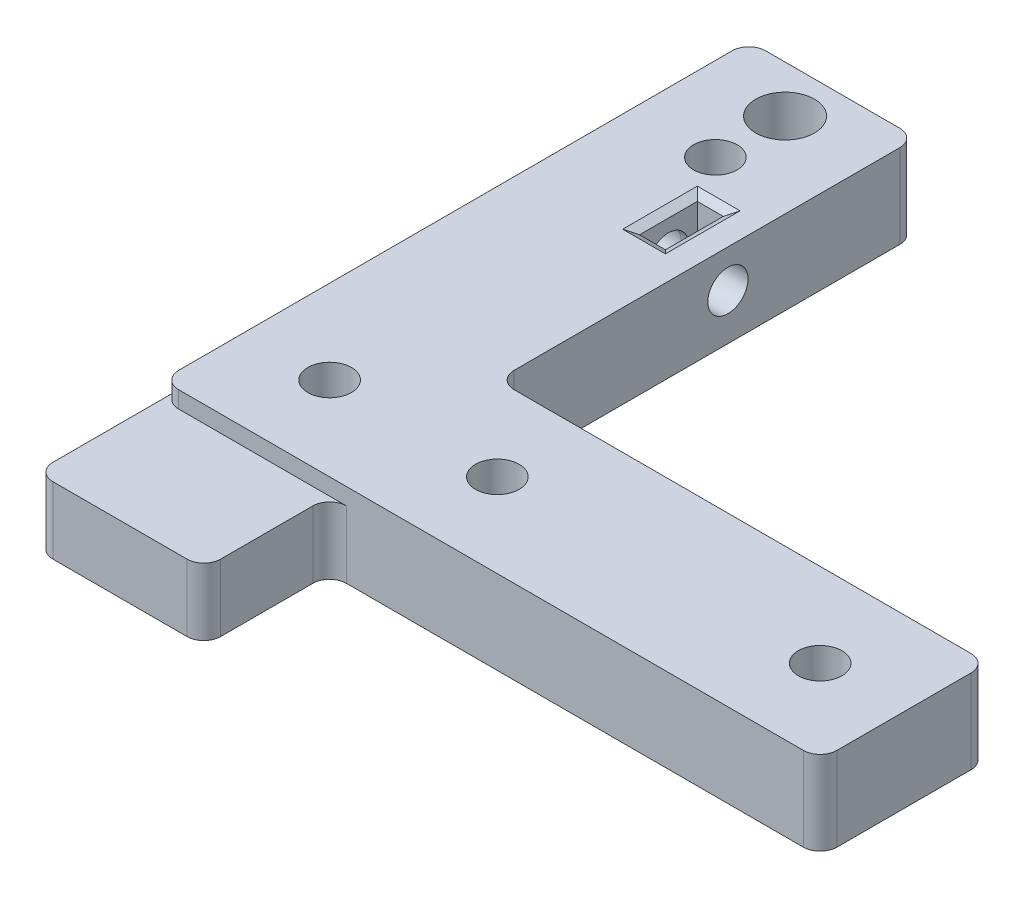
SolidWorks part; units mm, degrees
ref_plane "Front" through (0, 0, 0) normal (0, 0, 1) x (1, 0, 0)
ref_plane "Top" through (0, 0, 0) normal (0, 1, 0) x (1, 0, 0)
ref_plane "Right" through (0, 0, 0) normal (1, 0, 0) x (0, 0, -1)
sketch "Sketch1" plane through (0, 0, 0) normal (0, 1, 0) x (1, 0, 0)
  line L0 (0, 0) -> (78.5, 0)
  line L1 (78.5, 0) -> (78.5, 20)
  line L2 (78.5, 20) -> (20, 20)
  line L3 (20, 20) -> (20, 70)
  line L4 (20, 70) -> (0, 70)
  line L5 (0, 70) -> (0, 0)
  line L6 (78.5, 10) -> (0, 10) construction
  line L7 (10, 70) -> (10, 0) construction
  circle A0 centre (10, 56) radius 2.6
  circle A1 centre (68.5, 10) radius 2.6
  circle A2 centre (10, 10) radius 2.6
  circle A3 centre (30, 10) radius 2.6
  dimension "D5" = 5.2
  dimension "D6" = 10
  dimension "D7" = 20
  dimension "D1" = 78.5
  dimension "D2" = 70
  dimension "D3" = 14
  dimension "D4" = 20
extrude "Boss-Extrude1" add sketch "Sketch1" along normal blind 10
sketch "Sketch4" plane through (0, 0, 0) normal (-1, 0, 0) x (0, 0, 1)
  line L0 (-70, 10) -> (-70, 0) construction
  line L1 (-70, 10) -> (0, 10) construction
  circle A0 centre (-47.5, 5.5) radius 2.4
  dimension "D1" = 22.5
  dimension "D2" = 4.5
  dimension "D3" = 4.8
extrude "motor tensioning hole" cut sketch "Sketch4" against normal through all
sketch "Sketch10" plane through (0, 10, 0) normal (0, 1, 0) x (1, 0, 0)
  line L0 (20, 20) -> (20, 70) construction
  line L1 (0, 0) -> (20, 0)
  line L2 (0, 0) -> (0, -15)
  line L3 (0, -15) -> (20, -15)
  line L4 (20, 0) -> (20, -15)
  dimension "D1" = 15
extrude "Boss-Extrude3" add sketch "Sketch10" against normal blind 10
fillet "Fillet1" radius 2 8 edges at (0, 5, -70) (20, 5, -70) (20, 5, -20) (78.5, 5, 0) (78.5, 5, -20) (20, 5, 15) (20, 5, 0) (0, 5, 15)
chamfer "Chamfer2" distance 12 angle 5 1 edges at (0, 5.5, -45.1) first distance on face at (0, 5.5, -45.1)
sketch "Sketch17" plane through (20, 0, 0) normal (1, 0, 0) x (0, 0, -1)
  line L0 (44.05, 7.4919) -> (44.05, 10)
  line L1 (44.05, 3.5081) -> (47.5, 1.5163)
  line L2 (47.5, 1.5163) -> (50.95, 3.5081)
  line L3 (50.95, 3.5081) -> (50.95, 7.4919)
  line L4 (50.95, 7.4919) -> (47.5, 9.4837) construction
  line L5 (47.5, 9.4837) -> (44.05, 7.4919) construction
  line L6 (44.05, 7.4919) -> (44.05, 3.5081)
  line L7 (22, 10) -> (68, 10) construction
  line L8 (44.05, 10) -> (50.95, 10)
  line L9 (50.95, 10) -> (50.95, 7.4919)
  circle A0 centre (47.5, 5.5) radius 3.45 construction
  dimension "D1" = 6.9
extrude "Cut-Extrude8" cut sketch "Sketch17" against normal blind 3.1 from offset 4 offset against normal yes
chamfer "Chamfer3" distance 1 angle 30 4 edges at (14.45, 10, -44.05) (16, 10, -47.5) (14.45, 10, -50.95) (12.9, 10, -47.5) first distance on face at (10, 10, -7.4)
sketch "Sketch6" plane through (0, 10, 0) normal (0, 1, 0) x (1, 0, 0)
  line L0 (18, 70) -> (2, 70) construction
  line L1 (0, 68) -> (0, -13) construction
  circle A0 centre (9.8995, 64.4167) radius 3.5
  dimension "D1" = 5.5833
  dimension "D2" = 7
  dimension "D3" = 9.8995
extrude "M3 Screwhead Clearance" cut sketch "Sketch6" against normal blind 5
sketch "Sketch15" [suppressed] plane through (0, 10, 0) normal (0, 1, 0) x (1, 0, 0)
  line L0 (10, 56) -> (10, 63) construction
  line L1 (7.4, 56) -> (7.4, 63)
  line L2 (12.6, 56) -> (12.6, 63)
  line L3 (18, 70) -> (2, 70) construction
  line L4 (30, 10) -> (24.5, 10) construction
  line L7 (30, 7.4) -> (24.5, 7.4)
  line L8 (30, 12.6) -> (24.5, 12.6)
  arc A0 (7.4, 56) -> (12.6, 56) centre (10, 56) ccw
  arc A1 (12.6, 63) -> (7.4, 63) centre (10, 63) ccw
  circle A2 centre (10, 56) radius 2.6 construction
  arc A6 (30, 7.4) -> (30, 12.6) centre (30, 10) ccw
  arc A7 (24.5, 12.6) -> (24.5, 7.4) centre (24.5, 10) ccw
  circle A8 centre (10, 10) radius 2.6 construction
  circle A9 centre (30, 10) radius 2.6 construction
  point P3 (10, 59.5)
  point P15 (27.25, 10)
  dimension "D2" = 14.5
  dimension "D1" = 7
extrude "M5 Slots for Alternate Plate" [suppressed] cut sketch "Sketch15" against normal through all
mirror "Mirror1" [suppressed] of bodies 117 101
delete or keep bodies "Body-Delete/Keep 1" [suppressed] type delete bodies bodies 117
sketch "Sketch2" [suppressed] plane through (0, 0, 0) normal (0, 1, 0) x (1, 0, 0)
  line L6 (157, -13) -> (157, 68)
  line L7 (155, 70) -> (139, 70)
  line L8 (137, 68) -> (137, 22)
  line L9 (135, 20) -> (80.5, 20)
  line L10 (78.5, 18) -> (78.5, 2)
  line L11 (80.5, 0) -> (135, 0)
  line L12 (157, -13) -> (157, 68)
  line L13 (155, 70) -> (139, 70)
  line L14 (137, 68) -> (137, 22)
  line L15 (135, 20) -> (80.5, 20)
  line L16 (78.5, 18) -> (78.5, 2)
  line L17 (80.5, 0) -> (135, 0)
  line L20 (139, -15) -> (155, -15)
  line L21 (139, -15) -> (155, -15)
  line L22 (137, -2) -> (137, -13)
  line L23 (137, -2) -> (137, -13)
  circle A0 centre (147, 56) radius 2.6 construction
  circle A1 centre (147, 10) radius 2.6 construction
  circle A2 centre (88.5, 10) radius 2.6 construction
  circle A4 centre (147, 10) radius 2.6
  circle A5 centre (88.5, 10) radius 2.6
  circle A6 centre (127, 10) radius 2.6 construction
  arc A14 (157, 68) -> (155, 70) centre (155, 68) ccw
  arc A15 (157, 68) -> (155, 70) centre (155, 68) ccw
  arc A16 (139, 70) -> (137, 68) centre (139, 68) ccw
  arc A17 (139, 70) -> (137, 68) centre (139, 68) ccw
  arc A18 (135, 20) -> (137, 22) centre (135, 22) ccw
  arc A19 (135, 20) -> (137, 22) centre (135, 22) ccw
  arc A20 (80.5, 20) -> (78.5, 18) centre (80.5, 18) ccw
  arc A21 (80.5, 20) -> (78.5, 18) centre (80.5, 18) ccw
  arc A22 (78.5, 2) -> (80.5, 0) centre (80.5, 2) ccw
  arc A23 (78.5, 2) -> (80.5, 0) centre (80.5, 2) ccw
  arc A24 (155, -15) -> (157, -13) centre (155, -13) ccw
  arc A28 (155, -15) -> (157, -13) centre (155, -13) ccw
  arc A29 (137, -2) -> (135, 0) centre (135, -2) ccw
  arc A30 (137, -2) -> (135, 0) centre (135, -2) ccw
  arc A31 (137, -13) -> (139, -15) centre (139, -13) ccw
  arc A32 (137, -13) -> (139, -15) centre (139, -13) ccw
  circle A33 centre (147, 56) radius 2.6
  circle A34 centre (127, 10) radius 2.6
  dimension "D1" = 0
extrude "height bump" [suppressed] add sketch "Sketch2" against normal blind 10.2
sketch "Sketch16" [suppressed] plane through (0, 0, 0) normal (0, 1, 0) x (1, 0, 0)
  line L0 (132.5, 7.4) -> (127, 7.4) construction
  line L1 (127, 12.6) -> (132.5, 12.6) construction
  line L2 (144.4, 56) -> (144.4, 63) construction
  line L3 (149.6, 63) -> (149.6, 56) construction
  line L4 (132.5, 7.4) -> (127, 7.4)
  line L5 (127, 12.6) -> (132.5, 12.6)
  line L6 (144.4, 56) -> (144.4, 63)
  line L7 (149.6, 63) -> (149.6, 56)
  arc A0 (127, 12.6) -> (127, 7.4) centre (127, 10) ccw construction
  arc A1 (132.5, 7.4) -> (132.5, 12.6) centre (132.5, 10) ccw construction
  arc A2 (144.4, 56) -> (149.6, 56) centre (147, 56) ccw construction
  arc A3 (149.6, 63) -> (144.4, 63) centre (147, 63) ccw construction
  arc A4 (127, 12.6) -> (127, 7.4) centre (127, 10) ccw
  arc A5 (132.5, 7.4) -> (132.5, 12.6) centre (132.5, 10) ccw
  arc A6 (144.4, 56) -> (149.6, 56) centre (147, 56) ccw
  arc A7 (149.6, 63) -> (144.4, 63) centre (147, 63) ccw
extrude "slotted height bump cutout" [suppressed] cut sketch "Sketch16" against normal through all
sketch "Sketch12" [suppressed] plane through (157, 0, 0) normal (1, 0, 0) x (0, 0, -1)
  line L1 (-13, -10.2) -> (68, -10.2) construction
  line L2 (0, 10) -> (18, 10)
  line L3 (0, 10) -> (0, -10.2)
  line L4 (0, -10.2) -> (18, -10.2)
  line L5 (18, 10) -> (18, -10.2)
  dimension "D2" = 18
extrude "Limit Switch Cutout" [suppressed] cut sketch "Sketch12" against normal blind 5.75
sketch "Sketch3" [suppressed] plane through (151.25, 0, 0) normal (1, 0, 0) x (0, 0, -1)
  line L0 (70, 10) -> (0, 10) construction
  line L2 (-1.8564, 10) -> (11.9064, 10) construction
  line L3 (70, -10.2) -> (0, -10.2) construction
  line L4 (5.8, -7.2) -> (5.8, 5.8) construction
  line L5 (2.8, -10.2) -> (2.8, 10) construction
  line L7 (68, 10) -> (18, 10) construction
  circle A2 centre (5.8, 5.8) radius 1.5
  circle A3 centre (5.8, -7.2) radius 1.35
  dimension "D1" = 2.7
  dimension "D2" = 3
  dimension "D3" = 13
  dimension "D4" = 4.2
  dimension "D6" = 2.8
  dimension "D7" = 3
extrude "d2hw limit switch holes" [suppressed] cut sketch "Sketch3" against normal blind 7
chamfer "Chamfer1" [suppressed] distance 0.4 angle 75
sketch "Sketch9" plane through (0, 0, 0) normal (-1, 0, 0) x (0, 0, 1)
  line L0 (13, 2) -> (-44.0501, 2) construction
  line L1 (13, 0) -> (13, 10) construction
  line L2 (-44.0501, 2) -> (-44.0501, 5.5) construction
  line L3 (-68, 0) -> (13, 0) construction
  circle A0 centre (-47.5, 5.5) radius 3.4499 construction
  text T0 "LMS-04" font "Century Gothic" height in points 22
  dimension "D1" = 2
extrude "Cut-Extrude3" cut sketch "Sketch9" against normal blind 0.4
sketch "Sketch8" [suppressed] plane through (157, 0, 0) normal (1, 0, 0) x (0, 0, -1)
  line L0 (-0.4035, -7.2) -> (70, -7.2) construction
  line L2 (70, -10.2) -> (70, 10) construction
  line L3 (18, -10.2) -> (68, -10.2) construction
  text T0 "RMS-05" font "Century Gothic" height in points 22
  dimension "D1" = 3
extrude "Right Side Part Num Short" [suppressed] cut sketch "Sketch8" against normal blind 0.4
sketch "Sketch11" [suppressed] plane through (0, 10, 0) normal (0, 1, 0) x (1, 0, 0)
  line L0 (157, 68) -> (157, 18) construction
  line L1 (157, 0) -> (134.8301, 0)
  line L2 (157, 0) -> (157, -15)
  line L3 (157, -15) -> (134.8301, -15)
  line L4 (134.8301, 0) -> (134.8301, -15)
  line L7 (155, -15) -> (139, -15) construction
  line L8 (135, 0) -> (80.5, 0) construction
extrude "Cut-Extrude4" [suppressed] cut sketch "Sketch11" against normal offset from surface (12.2 mm away) 8 up to face at (9.8995, 10, -60.9167)
fillet "Fillet2" [suppressed] radius 2
sketch "Sketch13" [suppressed] plane through (151.25, 0, 0) normal (1, 0, 0) x (0, 0, -1)
  line L0 (5.8, 5.05) -> (5.8, -2.95) construction
  line L1 (5.8, 5.05) -> (5.8, 10) construction
  line L2 (16, 10) -> (0, 10) construction
  line L3 (0, 10) -> (0, -2.2) construction
  line L4 (-13, -10.2) -> (-2, -10.2) construction
  circle A0 centre (5.8, 5.05) radius 1.3
  circle A1 centre (5.8, -2.95) radius 1.3
  dimension "D1" = 7.25
  dimension "D3" = 2.6
  dimension "D2" = 8
  dimension "D4" = 5.8
extrude "compact switch holes" [suppressed] cut sketch "Sketch13" against normal blind 6
fillet "Fillet3" [suppressed] radius 1
sketch "Sketch14" plane through (0, 10, 0) normal (0, 1, 0) x (1, 0, 0)
  line L0 (2, -15) -> (18, -15) construction
  line L1 (0, -15) -> (22, -15)
  line L2 (0, -15) -> (0, 0)
  line L3 (0, 0) -> (22, 0)
  line L4 (22, -15) -> (22, 0)
extrude "Cut-Extrude7" cut sketch "Sketch14" against normal offset from surface (2 mm away) 8 up to face at (29.625, 0, -18.75)
fillet "Fillet4" radius 2 1 edges at (0, 9, 0)
